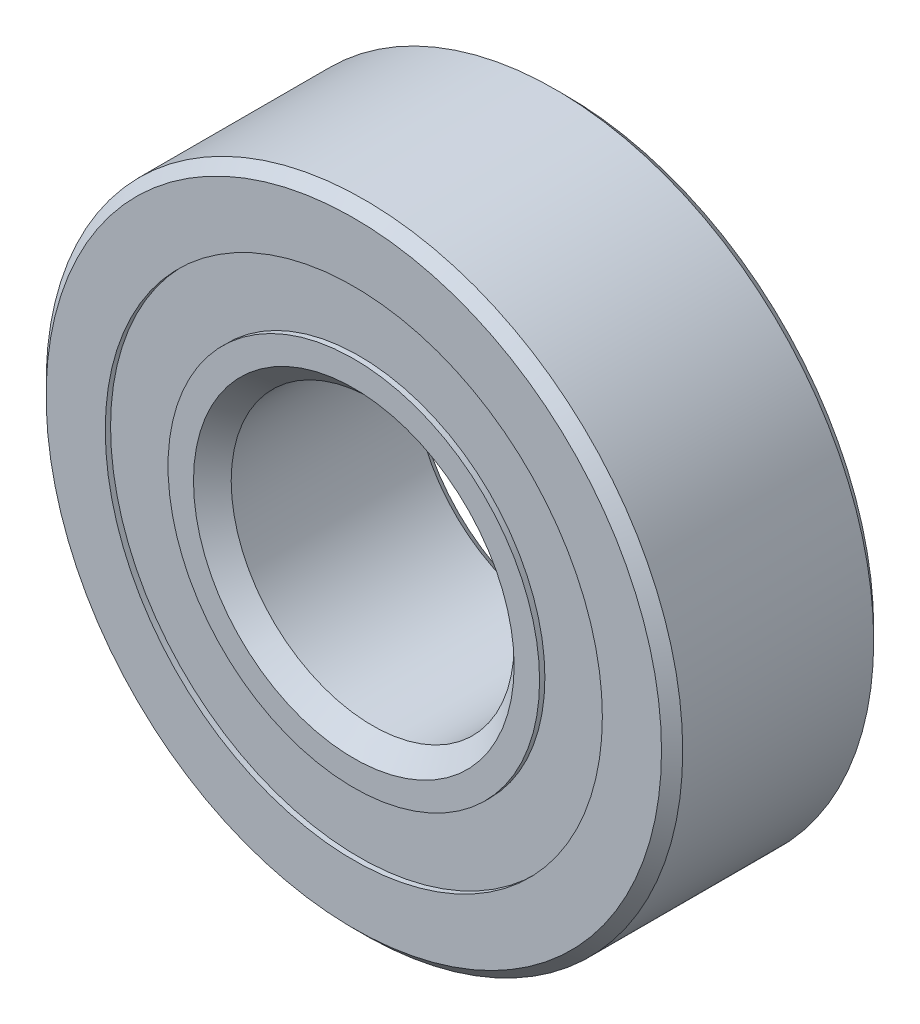
SolidWorks part; units mm, degrees
ref_plane "Front Plane" through (0, 0, 0) normal (0, 0, 1) x (1, 0, 0)
ref_plane "Top Plane" through (0, 0, 0) normal (0, 1, 0) x (1, 0, 0)
ref_plane "Right Plane" through (0, 0, 0) normal (1, 0, 0) x (0, 0, -1)
sketch "Sketch1" plane through (0, 0, 0) normal (1, 0, 0) x (0, 0, -1)
  line L0 (-4.7625, 0) -> (4.7625, 0) construction
  line L1 (0, 14.2875) -> (0, -14.2875) construction
  line L2 (4.2863, 14.2875) -> (-4.2863, 14.2875)
  line L3 (-4.2863, 14.2875) -> (-4.7625, 13.8112)
  line L4 (-4.7625, 13.8112) -> (-4.7625, 11.1561)
  line L5 (-4.7625, 11.1561) -> (-2.1167, 11.1561)
  line L6 (4.7625, 11.1561) -> (2.1167, 11.1561)
  line L7 (4.7625, 13.8112) -> (4.7625, 11.1561)
  line L8 (4.2863, 14.2875) -> (4.7625, 13.8112)
  line L9 (0, 14.2875) -> (0, 10.3187) construction
  line L10 (0, 10.3187) -> (0, 6.35) construction
  arc A0 (-2.1167, 11.1561) -> (2.1167, 11.1561) centre (0, 10.3187) cw
  point P14 (0, 6.35)
  dimension "Width" = 9.525
  dimension "OD" = 28.575
  dimension "D1" = 45
  dimension "D2" = 0.4763
  dimension "D3" = 4.2333
  dimension "D4" = 0.8374
revolve "Revolve1" add sketch "Sketch1" angle 360 about L0
sketch "Sketch2" plane through (0, 0, 0) normal (1, 0, 0) x (0, 0, -1)
  line L0 (-4.5244, 9.4814) -> (-2.1167, 9.4814)
  line L1 (-4.7625, 13.8112) -> (-4.7625, -13.8112) construction
  line L2 (-4.7625, 8.3388) -> (-4.5244, 8.3388) construction
  line L3 (-4.5244, 8.1007) -> (-3.6199, 7.1962)
  line L4 (-3.6199, 7.1962) -> (0, 7.1962)
  line L5 (0, 14.2875) -> (0, -14.2875) construction
  line L6 (0, 7.1962) -> (0, 8.0425)
  line L7 (0, 8.0425) -> (0, 6.35) construction
  line L8 (-4.7625, 9.4814) -> (-4.7625, 7.1962) construction
  line L9 (-4.7625, 7.1962) -> (-3.6199, 7.1962) construction
  line L10 (-4.5244, 9.4814) -> (-4.5244, 8.1007)
  line L11 (-4.5244, 9.4814) -> (-4.5244, 14.0494) construction
  line L12 (-4.2863, 14.2875) -> (-4.7625, 13.8112) construction
  arc A0 (-2.1167, 9.4814) -> (0, 8.0425) centre (0, 10.3187) ccw
  arc A1 (2.1167, 11.1561) -> (-2.1167, 11.1561) centre (0, 10.3187) ccw construction
  circle A2 centre (0, 10.3187) radius 2.2763 construction
  dimension "D1" = 45
revolve "Revolve2" [suppressed] add sketch "Sketch2" angle 360 about L0
sketch "Sketch3" plane through (0, 0, 0) normal (1, 0, 0) x (0, 0, -1)
  line L0 (-4.5244, 8.1007) -> (-3.6199, 7.1962)
  line L1 (-3.6199, 7.1962) -> (0, 7.1962)
  line L2 (0, 7.1962) -> (0, 8.0425)
  line L3 (-4.7625, 8.3388) -> (-4.7625, 7.1962)
  line L4 (-4.7625, 9.4814) -> (-4.7625, 7.1962) construction
  line L5 (-4.7625, 7.1962) -> (-3.9163, 6.35)
  line L6 (-3.9163, 6.35) -> (4.2862, 6.35)
  line L7 (4.2863, 14.2875) -> (4.2863, -14.2875) construction
  line L8 (4.2862, 6.35) -> (4.7625, 6.8263)
  line L9 (4.7625, -13.8112) -> (4.7625, 13.8112) construction
  line L10 (4.7625, 6.8263) -> (4.7625, 9.4814)
  line L11 (4.7625, 9.4814) -> (2.1167, 9.4814)
  line L12 (-4.7625, 8.3388) -> (-4.5244, 8.3388)
  line L13 (4.2863, 14.2875) -> (4.7625, 13.8112) construction
  line L14 (-4.5244, 8.3388) -> (-4.5244, 8.1007)
  circle A0 centre (0, 10.3187) radius 2.2763 construction
  arc A1 (2.1167, 9.4814) -> (0, 8.0425) centre (0, 10.3187) cw
revolve "Revolve3" add sketch "Sketch3" angle 360 about L0
sketch "Sketch4" plane through (0, 0, 0) normal (1, 0, 0) x (0, 0, -1)
  line L0 (-2.2763, 10.3187) -> (2.2763, 10.3187)
  circle A1 centre (0, 10.3187) radius 2.2763 construction
  arc A2 (-2.2763, 10.3187) -> (2.2763, 10.3187) centre (0, 10.3187) cw
  arc A3 (2.1167, 11.1561) -> (-2.1167, 11.1561) centre (0, 10.3187) ccw construction
revolve "Revolve4" add sketch "Sketch4" angle 360 about L0
ref_axis "Axis1" through (0, 0, -4.7625) along (0, 0, 1)
pattern_circular "CirPattern1" count 10 every 36 about axis through (0, 0, -4.7625) along (0, 0, 1) of bodies 104
sketch "Sketch5" plane through (0, 0, 0) normal (1, 0, 0) x (0, 0, -1)
  line L0 (-4.7625, 11.1561) -> (-2.1167, 11.1561) construction
  line L1 (-4.5244, 11.1561) -> (-2.2763, 11.1561)
  line L2 (-4.5244, 11.1561) -> (-4.5244, 8.3388)
  line L3 (-4.5244, 8.3388) -> (-2.2763, 8.3388)
  line L4 (-2.2763, 11.1561) -> (-2.2763, 8.3388)
  line L6 (-4.2863, 14.2875) -> (-4.7625, 13.8112) construction
  line L7 (0, 14.2875) -> (0, 6.35) construction
  line L8 (4.5244, 8.3388) -> (2.2763, 8.3388)
  line L9 (2.2763, 11.1561) -> (2.2763, 8.3388)
  line L10 (4.5244, 11.1561) -> (2.2763, 11.1561)
  line L11 (4.5244, 11.1561) -> (4.5244, 8.3388)
  circle A0 centre (0, 10.3187) radius 2.2763 construction
  point P10 (-4.5244, 14.0494)
revolve "Revolve5" add sketch "Sketch5" angle 360 about L0
equation "\"D2@Sketch1\" = \"Width@Sketch1\"*.05"
equation "\"D3@Sketch1\" = \"Width@Sketch1\"/2.25"
equation "\"D4@Sketch1\" = (((\"OD@Sketch1\"-\"Width@Sketch1\")/2)/3.25)/3.5"
equation "\"D2@CirPattern1\" = 360/\"Balls@CirPattern1\""
